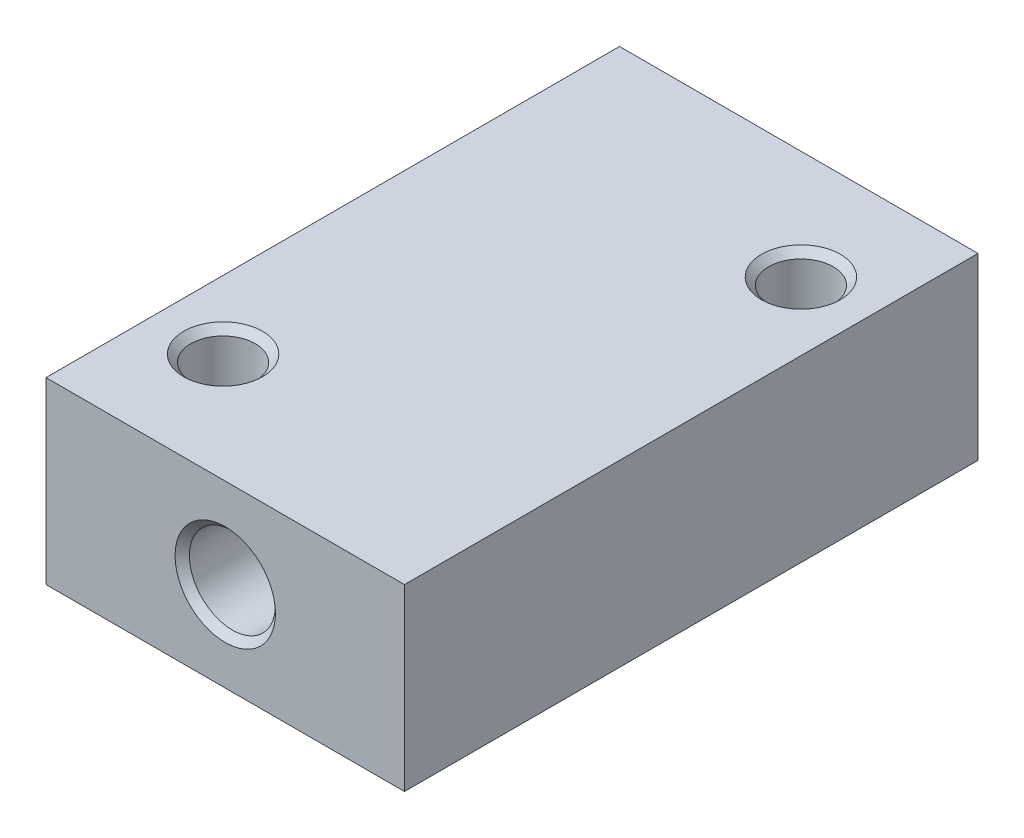
SolidWorks part; units mm, degrees
material "4032-T6"
ref_plane "Front Plane" through (0, 0, 0) normal (0, 0, 1) x (1, 0, 0)
ref_plane "Top Plane" through (0, 0, 0) normal (0, 1, 0) x (1, 0, 0)
ref_plane "Right Plane" through (0, 0, 0) normal (1, 0, 0) x (0, 0, -1)
sketch "Sketch1" plane through (0, 0, 0) normal (0, 1, 0) x (1, 0, 0)
  line L0 (6, 40) -> (6, -40) construction
  line L1 (-25, 40) -> (25, 40)
  line L2 (-25, 40) -> (-25, -40)
  line L3 (-25, -40) -> (25, -40)
  line L4 (25, 40) -> (25, -40)
  line L5 (-25, 40) -> (25, -40) construction
  line L6 (-25, -40) -> (25, 40) construction
  line L7 (6, 0) -> (25, 0) construction
  line L8 (15.5, 0) -> (15.5, 24.8) construction
  line L9 (0, 0) -> (-25, 15.625) construction
  circle A0 centre (15.5, 24.8) radius 4.5
  circle A1 centre (-15.5, -24.8) radius 4.5
  point P0 (0, 0)
  dimension "D4" = 9
  dimension "D1" = 80
  dimension "D2" = 50
  dimension "D3" = 6
extrude "Boss-Extrude1" add sketch "Sketch1" along normal blind 25
sketch "Sketch2" plane through (0, 0, 40) normal (0, 0, 1) x (1, 0, 0)
  line L0 (0, 12.5) -> (0, 0) construction
  line L1 (-25, 0) -> (25, 0) construction
  line L2 (0, 0) -> (25, 12.5) construction
  line L3 (25, 25) -> (25, 0) construction
  line L4 (25, 12.5) -> (0, 12.5) construction
  circle A0 centre (0, 12.5) radius 6
  dimension "D1" = 12
extrude "Cut-Extrude1" cut sketch "Sketch2" against normal through all
chamfer "Chamfer1" distance 1 angle 45 6 edges at (15.5, 0, -20.3) (-15.5, 0, 20.3) (15.5, 25, -20.3) (-15.5, 25, 20.3) (6, 12.5, -40) (6, 12.5, 40)
ref_axis "Axis1" through (0, 26.25, 0) along (0, -1, 0)
ref_plane "Plane1" through (0, 12.5, 0) normal (0, 1, 0) x (1, 0, 0)
sketch "Sketch3" plane through (0, 12.5, 0) normal (0, 1, 0) x (1, 0, 0)
  line L0 (-25, -40) -> (25, 40) construction
